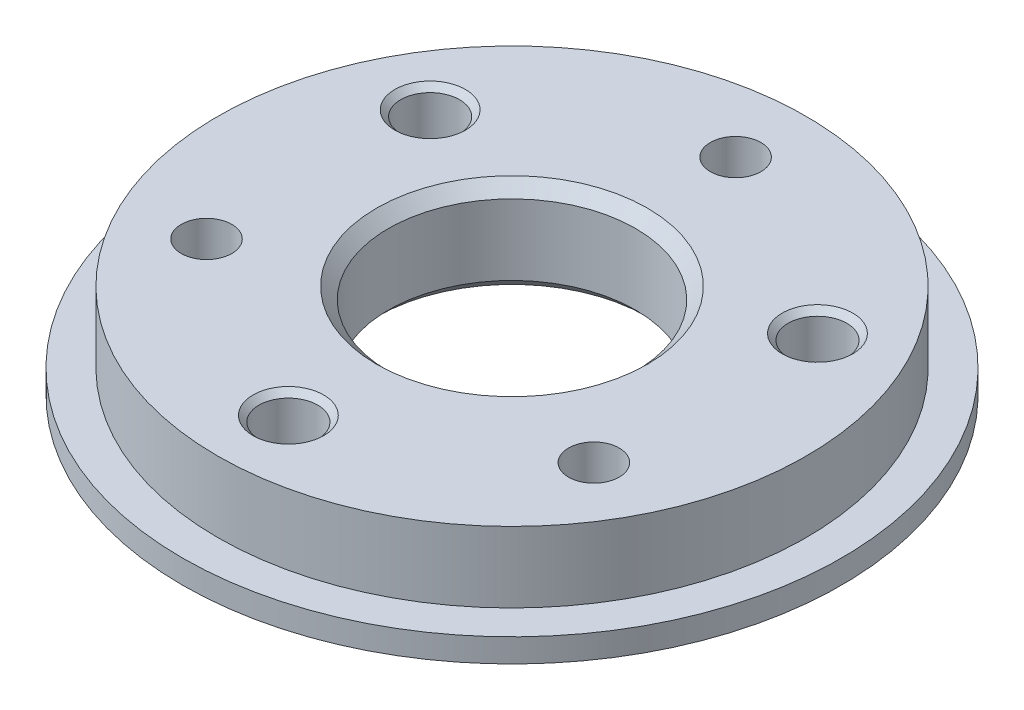
SolidWorks part; units mm, degrees
ref_plane "Front Plane" through (0, 0, 0) normal (0, 0, 1) x (1, 0, 0)
ref_plane "Top Plane" through (0, 0, 0) normal (0, 1, 0) x (1, 0, 0)
ref_plane "Right Plane" through (0, 0, 0) normal (1, 0, 0) x (0, 0, -1)
sketch "Sketch1" plane through (0, 0, 0) normal (0, 1, 0) x (1, 0, 0)
  circle A0 centre (0, 0) radius 18.5 construction
  circle A1 centre (0, 0) radius 10.5
  circle A2 centre (0, 0) radius 25
  dimension "D1" = 37
  dimension "D2" = 21
  dimension "D3" = 50
extrude "Boss-Extrude1" add sketch "Sketch1" along normal blind 6
sketch "Sketch2" plane through (0, 6, 0) normal (0, 1, 0) x (1, 0, 0)
  circle A0 centre (0, 0) radius 19 construction
  circle A1 centre (0, 19) radius 2.15
  circle A2 centre (16.4545, -9.5) radius 2.15
  circle A3 centre (-16.4545, -9.5) radius 2.15
  point P17 (0, 0)
  dimension "D1" = 38
  dimension "D2" = 4.3
  dimension "D3" = 3
extrude "Threaded Tapped Hole Cutouts" cut sketch "Sketch2" against normal through all
ref_axis "Axis1" through (0, 6, 0) along (0, -1, 0)
sketch "Sketch3" plane through (0, 6, 0) normal (0, 1, 0) x (1, 0, 0)
  circle A0 centre (0, 0) radius 19 construction
  circle A1 centre (0, -19) radius 2.5
  circle A2 centre (-16.4545, 9.5) radius 2.5
  circle A3 centre (16.4545, 9.5) radius 2.5
  point P11 (0, 0)
  dimension "D1" = 38
  dimension "D3" = 3
  dimension "D2" = 5
extrude "Pin Inserts Cutout" cut sketch "Sketch3" against normal blind 5
sketch "Sketch4" plane through (0, 0, 0) normal (0, -1, 0) x (1, 0, 0)
  circle A0 centre (0, 0) radius 10.5 construction
  circle A1 centre (0, 0) radius 10.5
  circle A2 centre (0, 0) radius 28
  dimension "D1" = 56
extrude "Boss-Extrude2" add sketch "Sketch4" along normal blind 2
chamfer "Chamfer1" distance 1 angle 45 2 edges at (0, -2, -10.5) (0, 6, 10.5)
sketch "Sketch5" plane through (0, -2, 0) normal (0, -1, 0) x (1, 0, 0)
  circle A0 centre (0, 0) radius 20 construction
  circle A1 centre (-20, 0) radius 1.25
  circle A2 centre (-9.9995, 17.3214) radius 1.25
  circle A3 centre (10.0015, 17.3214) radius 1.25
  circle A4 centre (20.002, 0) radius 1.25
  circle A5 centre (10.0015, -17.3214) radius 1.25
  circle A6 centre (-9.9995, -17.3214) radius 1.25
  point P21 (0.001, 0)
  dimension "D1" = 40
  dimension "D2" = 2.5
  dimension "D3" = 6
extrude "Cut-Extrude3" cut sketch "Sketch5" against normal blind 5
chamfer "Chamfer2" distance 0.5 angle 45 3 edges at (16.4545, 6, -7) (-16.4545, 6, -7) (0, 6, 21.5)
hole_wizard "M5x0.8 Tapped Hole1" positions "Sketch6" profile "Sketch7" tap size "M5x0.8" standard "ANSI Metric"
sketch "Sketch6" plane through (0, 6, 0) normal (0, 1, 0) x (1, 0, 0)
  point P0 (-16.4545, -9.5)
  point P3 (0, 19)
  point P6 (16.4545, -9.5)
sketch "Sketch7" plane through (-16.4545, 6, 9.5) normal (1, 0, 0) x (0, 0, 1)
  line L0 (0, 0) -> (0, 7.2618)
  line L1 (0, 7.2618) -> (2.1, 6)
  line L2 (2.1, 6) -> (2.1, 0)
  line L5 (2.1, 0) -> (0, 0)
  line L10 (0, 7.2618) -> (-2.1, 6) construction
  line L11 (0, -6.35) -> (0, 107.95) construction
  dimension "Tap Drill Dia." = 4.2
  dimension "Tap Drill Depth" = 6
  dimension "Drill Angle" = 118
cosmetic thread "Hole Thread1" parameters "D1"=10, "D2"=9.3504
cosmetic thread "Hole Thread2" parameters "D1"=10, "D2"=9.3504
cosmetic thread "Hole Thread3" parameters "D1"=10, "D2"=9.3504
sketch "Sketch10" plane through (0, -2, 0) normal (0, -1, 0) x (1, 0, 0)
  point P0 (20, 0)
  point P1 (10, -17.3205)
  point P6 (-10, -17.3205)
  point P7 (-20, 0)
  point P8 (-10, 17.3205)
  point P9 (10, 17.3205)
  point P10 (0, 0)
  dimension "D1" = 20
  dimension "D2" = 6
hole_wizard "M3x0.5 Tapped Hole2" positions "Sketch11" profile "Sketch12" tap size "M3x0.5" standard "ANSI Metric"
sketch "Sketch11" plane through (0, -2, 0) normal (0, -1, 0) x (-1, 0, 0)
  point P0 (10, -17.3205)
  point P3 (-10, -17.3205)
  point P6 (-20, 0)
  point P9 (-10, 17.3205)
  point P12 (9.9995, 17.3214)
  point P15 (20, 0)
sketch "Sketch12" plane through (-10, -2, 17.3205) normal (1, 0, 0) x (0, 0, -1)
  line L0 (0, 0) -> (0, 6.7511)
  line L1 (0, 6.7511) -> (1.25, 6)
  line L2 (1.25, 6) -> (1.25, 0)
  line L5 (1.25, 0) -> (0, 0)
  line L10 (0, 6.7511) -> (-1.25, 6) construction
  line L11 (0, -6.35) -> (0, 107.95) construction
  dimension "Tap Drill Dia." = 2.5
  dimension "Tap Drill Depth" = 6
  dimension "Drill Angle" = 118
cosmetic thread "Hole Thread4" parameters "D1"=4.5, "D2"=3
cosmetic thread "Hole Thread5" parameters "D1"=4.5, "D2"=3
cosmetic thread "Hole Thread6" parameters "D1"=4.5, "D2"=3
cosmetic thread "Hole Thread7" parameters "D1"=4.5, "D2"=3
cosmetic thread "Hole Thread8" parameters "D1"=4.5, "D2"=3
cosmetic thread "Hole Thread9" parameters "D1"=4.5, "D2"=3
equation "\"Inner Diameter\"= 21"
equation "\"D2@Sketch1\"=\"Inner Diameter\""
equation "\"Outer Diameter\"= 50"
equation "\"D3@Sketch1\"=\"Outer Diameter\""
equation "\"Margin\"=0.5"
equation "\"Hole Depth\"= 2"
equation "\"D1\"= \"Hole Depth\""
equation "\"Holes Position Diameter\"= 38"
equation "\"D1@Sketch2\"=\"Holes Position Diameter\""
equation "\"D1@Sketch3\"=\"Holes Position Diameter\""
